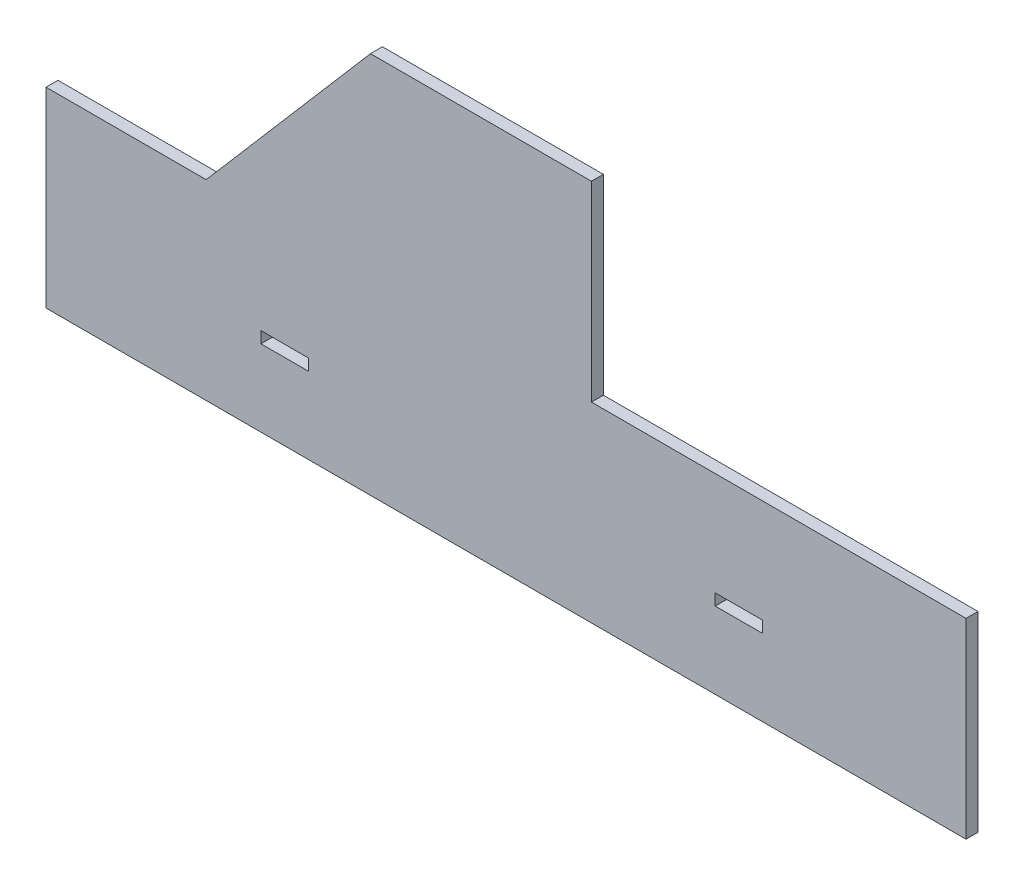
SolidWorks part; units mm, degrees
ref_plane "Front Plane" through (0, 0, 0) normal (0, 0, 1) x (1, 0, 0)
ref_plane "Top Plane" through (0, 0, 0) normal (0, 1, 0) x (1, 0, 0)
ref_plane "Right Plane" through (0, 0, 0) normal (1, 0, 0) x (0, 0, -1)
sketch "Sketch1" plane through (0, 0, 0) normal (0, 0, 1) x (1, 0, 0)
  line L0 (0, 0) -> (201.8088, 0)
  line L1 (201.8088, 0) -> (201.8088, 50.8)
  line L2 (201.8088, 50.8) -> (102.3141, 50.8)
  line L3 (102.3141, 50.8) -> (102.3141, 101.6)
  line L4 (102.3141, 101.6) -> (43.6394, 101.6)
  line L5 (43.6394, 101.6) -> (0, 50.8)
  line L6 (0, 50.8) -> (-42.5392, 50.8)
  line L7 (-42.5392, 50.8) -> (-42.5392, 0)
  line L8 (-42.5392, 0) -> (0, 0)
  dimension "D1" = 244.348
  dimension "D2" = 50.8
  dimension "D3" = 50.8
  dimension "D4" = 50.8
  dimension "D5" = 99.4947
extrude "Main Side" add sketch "Sketch1" along normal blind 3.175
sketch "Sketch2" plane through (0, 0, 3.175) normal (0, 0, 1) x (1, 0, 0)
  line L0 (-39.4912, 50.8) -> (-39.4912, 0) construction
  line L1 (-42.5392, 0) -> (201.8088, 0) construction
  line L15 (0, 50.8) -> (-42.5392, 50.8) construction
  line L16 (-42.5392, 50.8) -> (-42.5392, 0) construction
  line L19 (135.1973, 23.368) -> (147.7703, 23.368)
  line L20 (135.1973, 23.368) -> (135.1973, 20.32)
  line L21 (135.1973, 20.32) -> (147.7703, 20.32)
  line L22 (147.7703, 23.368) -> (147.7703, 20.32)
  line L26 (-39.4912, 18.5744) -> (201.8088, 18.5744) construction
  line L27 (201.8088, 0) -> (201.8088, 50.8) construction
  line L28 (81.1588, 18.5744) -> (81.1588, 101.6) construction
  line L29 (102.3141, 101.6) -> (43.6394, 101.6) construction
  line L30 (81.1588, 36.7006) -> (201.8088, 36.7006) construction
  line L31 (14.5473, 23.368) -> (14.5473, 20.32)
  line L32 (27.1203, 20.32) -> (14.5473, 20.32)
  line L33 (27.1203, 23.368) -> (27.1203, 20.32)
  line L34 (27.1203, 23.368) -> (14.5473, 23.368)
  point P26 (141.4838, 23.368)
  point P27 (141.4838, 36.7006)
  dimension "D1" = 12.573
  dimension "D2" = 3.048
  dimension "D3" = 20.32
  dimension "D4" = 3.048
extrude "Bottom Plate Holes" cut sketch "Sketch2" against normal through all
